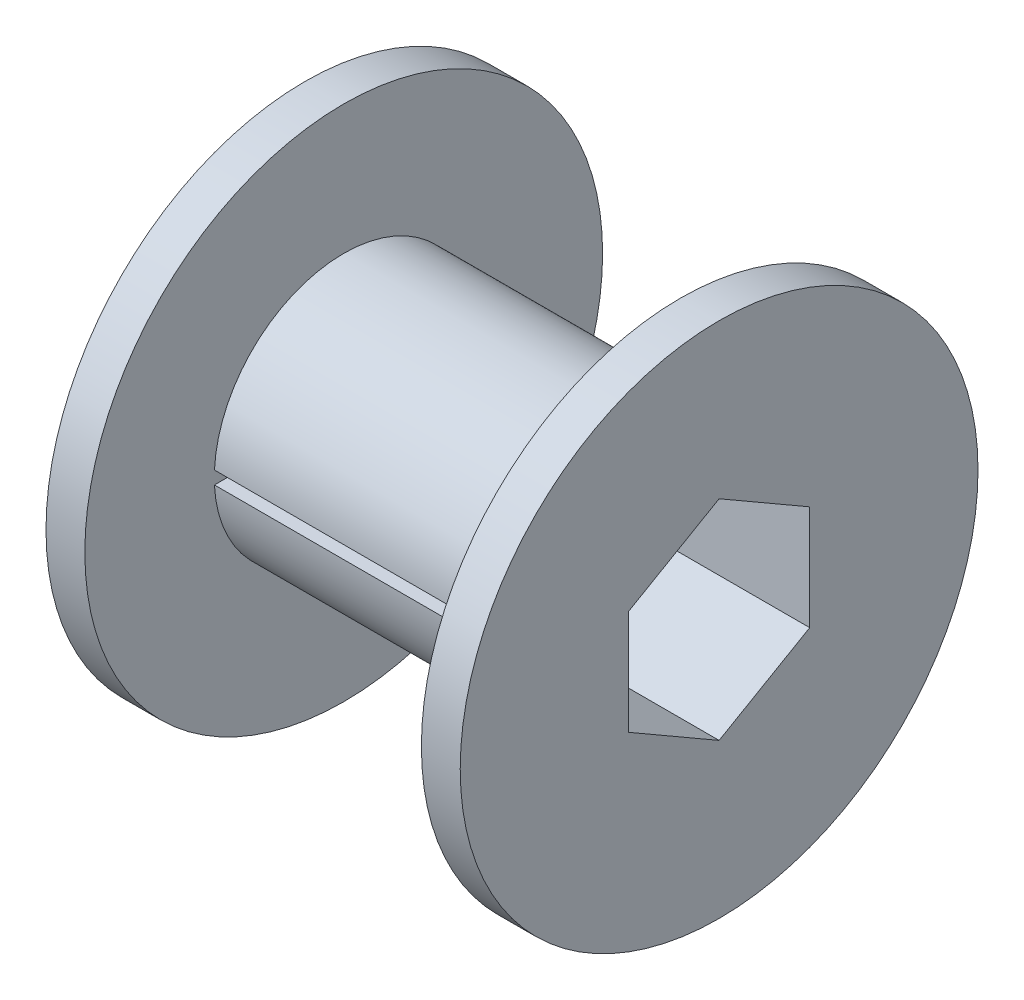
SolidWorks part; units mm, degrees
ref_plane "Front Plane" through (0, 0, 0) normal (0, 0, 1) x (1, 0, 0)
ref_plane "Top Plane" through (0, 0, 0) normal (0, 1, 0) x (1, 0, 0)
ref_plane "Right Plane" through (0, 0, 0) normal (1, 0, 0) x (0, 0, -1)
sketch "Sketch1" plane through (0, 0, 0) normal (1, 0, 0) x (0, 0, -1)
  circle A0 centre (0, 0) radius 2.5
  dimension "D1" = 5
extrude "Boss-Extrude1" add sketch "Sketch1" along normal mid plane 8
sketch "Sketch2" plane through (4, 0, 0) normal (1, 0, 0) x (0, 0, -1)
  circle A0 centre (0, 0) radius 5
  dimension "D1" = 10
extrude "Boss-Extrude2" add sketch "Sketch2" against normal blind 0.75
mirror "Mirror1" about plane through (0, 0, 0) normal (1, 0, 0) of "Boss-Extrude2"
sketch "Sketch3" plane through (0, 0, 0) normal (1, 0, 0) x (0, 0, -1)
  line L0 (1.75, 0) -> (1.75, 1.0104)
  line L1 (1.6, 0) -> (1.6, 0.9238) construction
  line L2 (1.6, -0.9238) -> (1.6, 0) construction
  line L3 (0.8, -1.3856) -> (1.6, -0.9238) construction
  line L4 (0, -1.8475) -> (0.8, -1.3856) construction
  line L5 (-0.8, -1.3856) -> (0, -1.8475) construction
  line L6 (-1.6, -0.9238) -> (-0.8, -1.3856) construction
  line L7 (-1.6, 0) -> (-1.6, -0.9238) construction
  line L8 (-1.6, 0.9238) -> (-1.6, 0) construction
  line L9 (-0.8, 1.3856) -> (-1.6, 0.9238) construction
  line L10 (0, 1.8475) -> (-0.8, 1.3856) construction
  line L11 (0.8, 1.3856) -> (0, 1.8475) construction
  line L12 (1.6, 0.9238) -> (0.8, 1.3856) construction
  line L13 (1.6, 0) -> (1.6, 0.9238) construction
  line L14 (1.6, -0.9238) -> (1.6, 0) construction
  line L15 (0.8, -1.3856) -> (1.6, -0.9238) construction
  line L16 (0, -1.8475) -> (0.8, -1.3856) construction
  line L17 (-0.8, -1.3856) -> (0, -1.8475) construction
  line L18 (-1.6, -0.9238) -> (-0.8, -1.3856) construction
  line L19 (-1.6, 0) -> (-1.6, -0.9238) construction
  line L20 (-1.6, 0.9238) -> (-1.6, 0) construction
  line L21 (-0.8, 1.3856) -> (-1.6, 0.9238) construction
  line L22 (0, 1.8475) -> (-0.8, 1.3856) construction
  line L23 (0.8, 1.3856) -> (0, 1.8475) construction
  line L24 (1.6, 0.9238) -> (0.8, 1.3856) construction
  line L25 (1.75, 1.0104) -> (0.875, 1.5155)
  line L26 (0.875, 1.5155) -> (0, 2.0207)
  line L27 (0, 2.0207) -> (-0.875, 1.5155)
  line L28 (-0.875, 1.5155) -> (-1.75, 1.0104)
  line L29 (-1.75, 1.0104) -> (-1.75, 0)
  line L30 (-1.75, 0) -> (-1.75, -1.0104)
  line L31 (-1.75, -1.0104) -> (-0.875, -1.5155)
  line L32 (-0.875, -1.5155) -> (0, -2.0207)
  line L33 (0, -2.0207) -> (0.875, -1.5155)
  line L34 (0.875, -1.5155) -> (1.75, -1.0104)
  line L35 (1.75, -1.0104) -> (1.75, 0)
  dimension "D1" = 0.15
extrude "M1.6 Nut" cut sketch "Sketch3" against normal through all both and the other way through all
sketch "Sketch5" plane through (0, 0, 0) normal (0, 0, 1) x (1, 0, 0)
  line L0 (3.25, 2.5) -> (3.25, -2.5) construction
  line L1 (3.25, 0.125) -> (-3.25, 0.125)
  line L2 (3.25, 0.125) -> (3.25, -0.125)
  line L3 (3.25, -0.125) -> (-3.25, -0.125)
  line L12 (-3.25, 0.125) -> (-3.25, -0.125)
  line L13 (3.25, 0.125) -> (-3.25, -0.125) construction
  line L14 (3.25, -0.125) -> (-3.25, 0.125) construction
  point P2 (0, 0)
  point P9 (0, 0)
  dimension "D1" = 0.25
extrude "Cut-Extrude1" cut sketch "Sketch5" along normal through all
